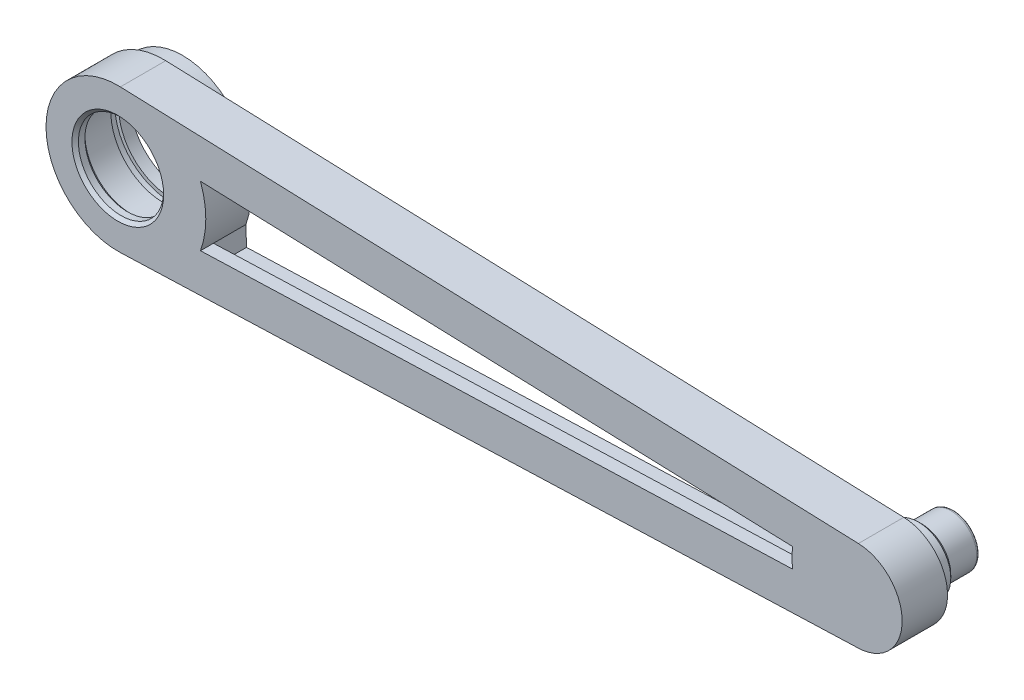
SolidWorks part; units mm, degrees
material "PEI"
ref_plane "前视基准面" through (0, 0, 0) normal (0, 0, 1) x (1, 0, 0)
ref_plane "上视基准面" through (0, 0, 0) normal (0, 1, 0) x (1, 0, 0)
ref_plane "右视基准面" through (0, 0, 0) normal (1, 0, 0) x (0, 0, -1)
other "Configuration Table"
sketch "草图1" plane through (0, 0, 0) normal (0, 0, 1) x (1, 0, 0)
  line L0 (0, 0) -> (114, 0) construction
  line L1 (0.3959, 11.0679) -> (114.2502, 6.9955)
  line L2 (0.3963, -11.0679) -> (114, -7)
  circle A0 centre (114, 0) radius 7
  circle A1 centre (0, 0) radius 8.075
  circle A2 centre (0, 0) radius 11.075
  dimension "D1" = 16.15
  dimension "D3" = 14
  dimension "D2" = 3
  dimension "D4" = 114
extrude "凸台-拉伸1" add sketch "草图1" along normal blind 7 contours A1 A2 | A2 L0 A0 L1 | L0 A2 L2 A0 | A0 region at (7.7447, -7.4723, 0) region at (55.374, 4.6572, 0) region at (55.3681, -4.6561, 0) region at (109.277, 4.895, 0)
sketch "草图2" plane through (0, 0, 7) normal (0, 0, 1) x (1, 0, 0)
  circle A0 centre (0, 0) radius 8.075 construction
  circle A1 centre (0, 0) radius 8.075
  circle A2 centre (0, 0) radius 6.575
  dimension "D1" = 1.5
extrude "凸台-拉伸2" add sketch "草图2" against normal blind 2
sketch "草图3" plane through (0, 0, 0) normal (0, 0, -1) x (-1, 0, 0)
  arc A0 (-114.2502, 6.9955) -> (-114, -7) centre (-114, 0) ccw construction
  arc A1 (-114.2502, 6.9955) -> (-114, -7) centre (-114, 0) ccw
  circle A2 centre (-114, 0) radius 4
  dimension "D1" = 8
extrude "凸台-拉伸3" add sketch "草图3" along normal blind 10 contours A2 region at (114, 0, 0)
sketch "草图4" plane through (0, 0, 0) normal (0, 0, -1) x (-1, 0, 0)
  circle A0 centre (-114, 0) radius 4 construction
  circle A1 centre (-114, 0) radius 4
  circle A2 centre (-114, 0) radius 5
  dimension "D1" = 1
extrude "凸台-拉伸4" add sketch "草图4" along normal blind 3
chamfer "倒角1" distance 0.5 angle 45 4 edges at (6.575, 0, 7) (6.575, 0, 5) (109, 0, -3) (110, 0, -10)
chamfer "倒角2" [suppressed] distance 1 angle 45
sketch "草图5" plane through (0, 0, 0) normal (0, 0, -1) x (-1, 0, 0)
  line L0 (-0.1738, 5.072) -> (-119.0901, 0.9975)
  line L1 (-118.9996, -0.9965) -> (-0.174, -5.072)
  line L2 (-114, -7) -> (-0.3963, -11.0679)
  line L3 (-114, -7) -> (-0.3963, -11.0679)
  line L8 (-0.3959, 11.0679) -> (-114.2502, 6.9955)
  line L9 (-0.3959, 11.0679) -> (-114.2502, 6.9955)
  arc A0 (-119.0901, 0.9975) -> (-118.9996, -0.9965) centre (-119.0945, -0.0017) ccw
  arc A1 (-0.174, -5.072) -> (-0.1738, 5.072) centre (0, 0) ccw
  arc A2 (-0.3963, -11.0679) -> (-0.3959, 11.0679) centre (0, 0) ccw
  arc A3 (-0.3963, -11.0679) -> (-0.3959, 11.0679) centre (0, 0) ccw
  circle A6 centre (-114, 0) radius 5 construction
  arc A12 (-114.2502, 6.9955) -> (-114, -7) centre (-114, 0) ccw
  arc A13 (-114.2502, 6.9955) -> (-114, -7) centre (-114, 0) ccw
  circle A30 centre (0, 0) radius 8.575
  circle A31 centre (-114, 0) radius 5
  circle A32 centre (-114, 0) radius 10
  circle A33 centre (0, 0) radius 13.575
  dimension "D1" = 0
  dimension "D3" = 5
extrude "切除-拉伸1" cut sketch "草图5" against normal up to surface (7 mm away) contours A33 L0 A32 L1 region at (51.0032, 0.0009, 0) up to face at (7.075, 0, 7)
sketch "草图6" plane through (0, 0, 0) normal (0, 0, -1) x (-1, 0, 0)
  line L0 (-104.1142, -1.507) -> (-12.7572, -4.6404) construction
  line L1 (-12.7571, 4.6409) -> (-104.1148, 1.5106) construction
  line L2 (-104.1142, -1.507) -> (-12.7572, -4.6404)
  line L3 (-12.7571, 4.6409) -> (-104.1148, 1.5106)
  line L4 (-12.8598, 7.6391) -> (-104.2175, 4.5089)
  line L5 (-104.217, -4.5053) -> (-12.8601, -7.6387)
  line L6 (-104.2175, 4.5089) -> (-104.1148, 1.5106)
  line L7 (-104.1142, -1.507) -> (-104.217, -4.5053)
  line L8 (-12.8598, 7.6391) -> (-12.7571, 4.6409)
  line L9 (-12.7572, -4.6404) -> (-12.8601, -7.6387)
  dimension "D1" = 3
extrude "切除-拉伸2" cut sketch "草图6" against normal blind 5
sketch "草图7" plane through (0, 0, 0) normal (0, 1, 0) x (1, 0, 0)
  line L0 (117.5, 10) -> (110.5, 10) construction
  line L1 (117.5, 10) -> (110.5, 10)
  line L2 (114, 10) -> (114, 0.7286) construction
  line L4 (110.3, 9) -> (110, 9)
  line L5 (110.3, 9) -> (110.3, 8)
  line L6 (110.3, 8) -> (110, 8)
  line L7 (110, 9) -> (110, 8)
  dimension "D1" = 1
  dimension "D2" = 4
  dimension "D3" = 3.7
  dimension "D4" = 2
revolve "切除-旋转1" [suppressed] cut sketch "草图7" angle 360 about L2
sketch "草图8" plane through (0, 0, -10) normal (0, 0, -1) x (-1, 0, 0)
  circle A0 centre (-114, 0) radius 4 construction
  circle A1 centre (-114, 0) radius 4
extrude "切除-拉伸3" cut sketch "草图8" against normal blind 2
fillet "圆角1" radius 0.5 1 edges at (110, 0, -8)
sketch "草图9" plane through (0, 0, -8) normal (0, 0, -1) x (-1, 0, 0)
  circle A0 centre (-114, 0) radius 2.2
  dimension "D1" = 4.4
extrude "切除-拉伸4" cut sketch "草图9" against normal blind 10
sketch "草图10" plane through (0, 0, 0) normal (0, 0, -1) x (-1, 0, 0)
  circle A0 centre (0, 0) radius 10.075
  circle A1 centre (0, 0) radius 8.075 construction
  circle A2 centre (0, 0) radius 8.075
  dimension "D1" = 2
extrude "凸台-拉伸5" add sketch "草图10" along normal blind 3
sketch "草图11" plane through (0, 0, 0) normal (0, 1, 0) x (1, 0, 0)
  line L0 (8.075, 3) -> (-8.075, 3) construction
  line L1 (5.1574, 1.2) -> (8.65, 1.2)
  line L2 (5.1574, 1.2) -> (5.1574, 0)
  line L3 (5.1574, 0) -> (8.65, 0)
  line L4 (8.65, 1.2) -> (8.65, 0)
  line L5 (0, 0) -> (0, 7.7818) construction
  dimension "D1" = 1.2
  dimension "D2" = 8.65
  dimension "D3" = 3
revolve "切除-旋转2" cut sketch "草图11" angle 360 about L5 region at (6.9037, 0, -0.6)
equation "\"D4@草图1\"= \"连接杆_前_长度\""
equation "\"连接杆_前_长度\"= 114"
